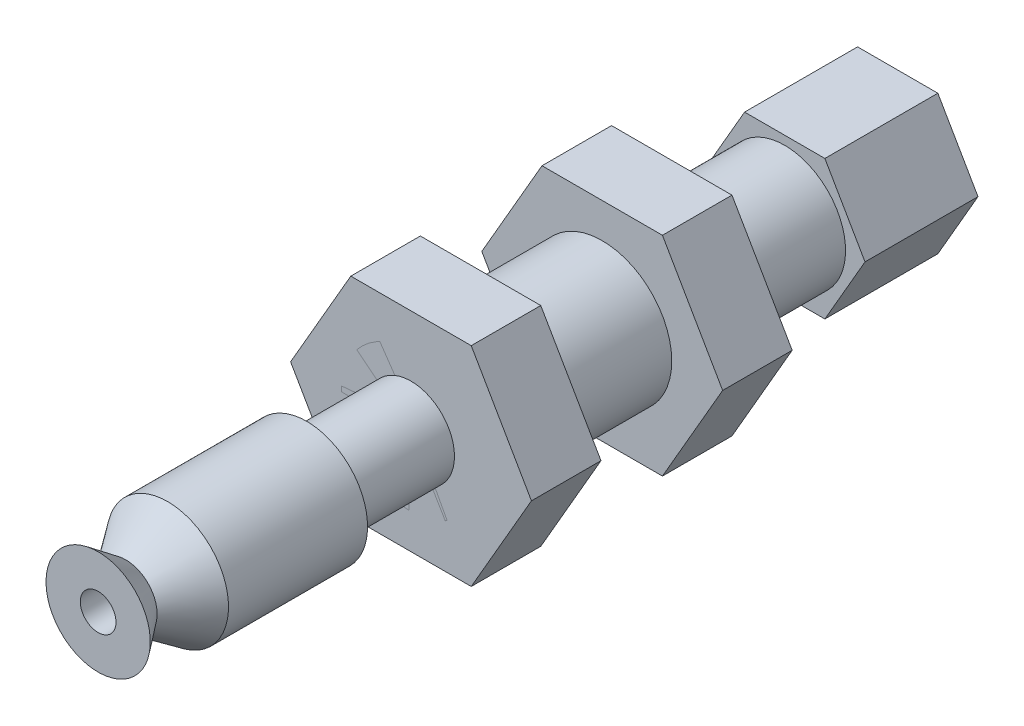
SolidWorks part; units mm, degrees
material "SKD11淬火HRC56-60"
ref_plane "前基準面" through (0, 0, 0) normal (0, 0, 1) x (1, 0, 0)
ref_plane "上基準面" through (0, 0, 0) normal (0, 1, 0) x (1, 0, 0)
ref_plane "右基準面" through (0, 0, 0) normal (1, 0, 0) x (0, 0, -1)
sketch "草图1" plane through (0, 0, 0) normal (0, 0, 1) x (1, 0, 0)
  circle A0 centre (0, 0) radius 3.5
  dimension "D1" = 7
extrude "凸台-拉伸1" add sketch "草图1" along normal blind 6.5
sketch "草图2" plane through (0, 0, 0) normal (0, 0, -1) x (-1, 0, 0)
  line L0 (3.575, 0) -> (-3.575, 0) construction
  line L1 (-4.6188, 0) -> (-2.3094, -4)
  line L2 (-2.3094, -4) -> (2.3094, -4)
  line L3 (2.3094, -4) -> (4.6188, 0)
  line L4 (4.6188, 0) -> (2.3094, 4)
  line L5 (2.3094, 4) -> (-2.3094, 4)
  line L6 (-2.3094, 4) -> (-4.6188, 0)
  circle A0 centre (0, 0) radius 4 construction
  dimension "D1" = 8
extrude "凸台-拉伸2" add sketch "草图2" along normal blind 6.5
sketch "草图3" plane through (0, 0, 6.5) normal (0, 0, 1) x (1, 0, 0)
  circle A0 centre (0, 0) radius 4
  dimension "D1" = 8
extrude "凸台-拉伸3" add sketch "草图3" along normal blind 15
sketch "草图4" plane through (0, 0, 6.5) normal (0, 0, -1) x (-1, 0, 0)
  line L0 (-2.3094, 4) -> (-4.6188, 0) construction
  line L1 (-3.4641, 6) -> (-6.9282, 0)
  line L2 (-6.9282, 0) -> (-3.4641, -6)
  line L3 (-3.4641, -6) -> (3.4641, -6)
  line L4 (3.4641, -6) -> (6.9282, 0)
  line L5 (6.9282, 0) -> (3.4641, 6)
  line L6 (3.4641, 6) -> (-3.4641, 6)
  circle A0 centre (0, 0) radius 6 construction
  dimension "D1" = 12
extrude "凸台-拉伸4" add sketch "草图4" against normal blind 4 separate body
sketch "草图5" plane through (0, 0, 21.5) normal (0, 0, 1) x (1, 0, 0)
  line L6 (3.4641, 6) -> (-3.4641, 6)
  line L7 (-3.4641, 6) -> (-6.9282, 0)
  line L8 (-6.9282, 0) -> (-3.4641, -6)
  line L9 (-3.4641, -6) -> (3.4641, -6)
  line L10 (3.4641, -6) -> (6.9282, 0)
  line L11 (6.9282, 0) -> (3.4641, 6)
  line L12 (3.4641, 6) -> (-3.4641, 6)
  line L13 (-3.4641, 6) -> (-6.9282, 0)
  line L14 (-6.9282, 0) -> (-3.4641, -6)
  line L15 (-3.4641, -6) -> (3.4641, -6)
  line L16 (3.4641, -6) -> (6.9282, 0)
  line L17 (6.9282, 0) -> (3.4641, 6)
  dimension "D1" = 0
extrude "凸台-拉伸5" add sketch "草图5" against normal blind 4 separate body
sketch "草图6" plane through (0, 0, 21.5) normal (0, 0, 1) x (1, 0, 0)
  circle A0 centre (0, 0) radius 2.5
  dimension "D1" = 5
extrude "凸台-拉伸6" add sketch "草图6" along normal blind 6 separate body
ref_axis "基准轴1" through (0, 0, 27.5) along (0, 0, -1)
sketch "草图7" plane through (0, 0, 0) normal (0, 1, 0) x (1, 0, 0)
  line L0 (0, -27.5) -> (0, -39.5)
  line L1 (0, -27.5) -> (0, -21.5) construction
  line L2 (0, -27.5) -> (3.5, -27.5)
  line L3 (3.5, -27.5) -> (3.5, -35.5)
  line L4 (3.5, -35.5) -> (1.8, -37.9068)
  line L5 (1.8, -37.9068) -> (3, -39.5)
  line L6 (3, -39.5) -> (0, -39.5)
  line L7 (-2.5, -27.5) -> (2.5, -27.5) construction
  dimension "D1" = 3.5
  dimension "D2" = 12
  dimension "D3" = 8
  dimension "D4" = 1.8
  dimension "D5" = 3
revolve "旋转1" add sketch "草图7" angle 360 about L0
hole_wizard "M5 螺纹孔1" positions "草图9" profile "草图8" tap size "M5" standard "ISO"
sketch "草图9" plane through (0, 0, -6.5) normal (0, 0, -1) x (-1, 0, 0)
  point P0 (0, 0)
sketch "草图8" plane through (0, 0, -6.5) normal (1, 0, 0) x (0, 1, 0)
  line L0 (0, 0) -> (0, 13.6618)
  line L1 (0, 13.6618) -> (2.1, 12.4)
  line L2 (2.1, 12.4) -> (2.1, 0)
  line L5 (2.1, 0) -> (0, 0)
  line L10 (0, 13.6618) -> (-2.1, 12.4) construction
  line L11 (0, -6.35) -> (0, 107.95) construction
  dimension "螺纹孔钻头直径" = 4.2
  dimension "螺纹孔钻头深度" = 12.4
  dimension "导头角度" = 118
cosmetic thread "孔螺蚊线1" parameters "D1"=10, "D2"=5
sketch "草图10" plane through (0, 0, 39.5) normal (0, 0, 1) x (1, 0, 0)
  circle A0 centre (0, 0) radius 1.0268
extrude "切除-拉伸1" cut sketch "草图10" against normal through all
